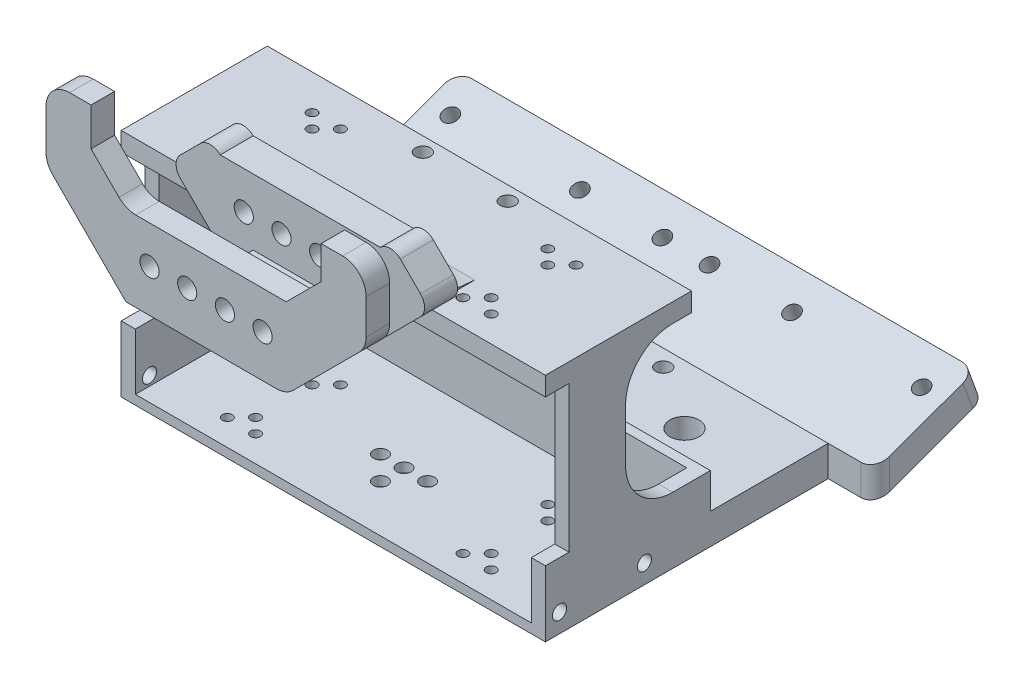
SolidWorks part; units mm, degrees
ref_plane "前视基准面" through (0, 0, 0) normal (0, 0, 1) x (1, 0, 0)
ref_plane "上视基准面" through (0, 0, 0) normal (0, 1, 0) x (1, 0, 0)
ref_plane "右视基准面" through (0, 0, 0) normal (1, 0, 0) x (0, 0, -1)
other "Configuration Table"
sketch "草图1" plane through (0, 0, 0) normal (0, 1, 0) x (1, 0, 0)
  line L1 (-45, 23) -> (45, 23)
  line L2 (-45, 23) -> (-45, -23)
  line L3 (-45, -23) -> (45, -23)
  line L4 (45, 23) -> (45, -23)
  line L5 (-45, 23) -> (45, -23) construction
  line L6 (-45, -23) -> (45, 23) construction
  point P0 (0, 0)
  dimension "D1" = 90
  dimension "D2" = 46
extrude "凸台-拉伸1" add sketch "草图1" along normal blind 4
sketch "草图3" plane through (0, 0, 23) normal (0, 0, 1) x (1, 0, 0)
  line L0 (-45, 0) -> (45, 0) construction
  line L1 (-17, 0) -> (17, 0)
  line L2 (-17, 0) -> (-17, 17) construction
  line L3 (17, 0) -> (17, 17) construction
  line L4 (-17, 17) -> (17, 17)
  line L6 (17, 0) -> (27.6066, 10.6066)
  line L7 (17, 17) -> (19.1066, 19.1066)
  line L9 (27.6066, 10.6066) -> (19.1066, 19.1066)
  line L10 (0, 0) -> (0, 17) construction
  line L11 (-17, 17) -> (-19.1066, 19.1066)
  line L12 (-27.6066, 10.6066) -> (-19.1066, 19.1066)
  line L13 (-17, 0) -> (-27.6066, 10.6066)
  point P0 (-17, 0)
  point P1 (17, 0)
  dimension "D1" = 17
  dimension "D2" = 17
  dimension "D3" = 17
  dimension "D4" = 45
  dimension "D5" = 15
extrude "凸台-拉伸2" add sketch "草图3" along normal blind 7
sketch "草图4" plane through (0, 0, 30) normal (0, 0, 1) x (1, 0, 0)
  line L0 (-18.5, 1.5) -> (18.5, 1.5) construction
  line L1 (-17, 0) -> (17, 0) construction
  line L3 (-27.6066, 10.6066) -> (-17, 0) construction
  line L4 (-10, 3) -> (10, 3)
  line L9 (17, 0) -> (27.6066, 10.6066) construction
  line L10 (-10, 3) -> (-10, 0)
  line L11 (-10, 0) -> (10, 0)
  line L12 (10, 3) -> (10, 0)
  line L13 (-10, 3) -> (10, 0) construction
  line L14 (-10, 0) -> (10, 3) construction
  point P8 (0, 1.5)
  dimension "D1" = 1.5
  dimension "D2" = 20
extrude "凸台-拉伸3" add sketch "草图4" along normal blind 15
sketch "草图5" plane through (0, 0, 45) normal (0, 0, 1) x (1, 0, 0)
  line L4 (-33.9632, 25.4632) -> (-33.9632, 32.4632)
  line L6 (-17, 0) -> (-27.6066, 10.6066)
  line L7 (-27.6066, 10.6066) -> (-17, 0) construction
  line L9 (-19.1066, 19.1066) -> (-17, 17)
  line L10 (-33.9632, 32.4632) -> (-24.4099, 32.4632)
  line L11 (-24.4099, 32.4632) -> (-24.4099, 24.4099)
  line L12 (-17, 17) -> (17, 17)
  line L13 (17, 17) -> (19.1066, 19.1066)
  line L16 (27.6066, 10.6066) -> (17, 0)
  line L17 (17, 0) -> (-17, 0)
  line L19 (-27.6066, 10.6066) -> (-38.2132, 21.2132) construction
  line L20 (-19.1066, 19.1066) -> (-29.7132, 29.7132) construction
  line L21 (-38.2132, 21.2132) -> (-29.7132, 29.7132) construction
  line L23 (19.1066, 19.1066) -> (29.7132, 29.7132) construction
  line L24 (27.6066, 10.6066) -> (38.2132, 21.2132) construction
  line L25 (29.7132, 29.7132) -> (38.2132, 21.2132) construction
  line L27 (24.4099, 24.4099) -> (24.4099, 31.4099)
  line L28 (24.4099, 31.4099) -> (33.9632, 31.4099)
  line L29 (33.9632, 31.4099) -> (33.9632, 25.4632)
  line L30 (-24.4099, 24.4099) -> (-19.1066, 19.1066)
  line L31 (19.1066, 19.1066) -> (24.4099, 24.4099)
  line L33 (-33.9632, 25.4632) -> (-33.9632, 16.9632)
  line L34 (-33.9632, 16.9632) -> (-27.6066, 10.6066)
  line L36 (33.9632, 25.4632) -> (33.9632, 16.9632)
  line L37 (33.9632, 16.9632) -> (27.6066, 10.6066)
  dimension "D1" = 15
  dimension "D2" = 15
  dimension "D3" = 7
  dimension "D4" = 7
extrude "凸台-拉伸4" add sketch "草图5" along normal blind 5
sketch "草图6" plane through (0, 0, 50) normal (0, 0, 1) x (1, 0, 0)
  line L0 (-20, 9) -> (20, 9) construction
  line L2 (-17, 0) -> (17, 0) construction
  circle A0 centre (-12, 9) radius 2.03
  circle A1 centre (-4, 9) radius 2.03
  circle A2 centre (4, 9) radius 2.03
  circle A3 centre (12, 9) radius 2.03
  point P6 (-12, 9)
  point P7 (-4, 9)
  point P8 (4, 9)
  point P9 (12, 9)
  point P10 (0, 9)
  dimension "D5" = 9
  dimension "D1" = 4
  dimension "D2" = 4
  dimension "D3" = 8
  dimension "D4" = 8
extrude "切除-拉伸2" cut sketch "草图6" against normal up to surface (27 mm away) up to face at (0, 12.6783, 23)
sketch "草图8" plane through (0, 0, 23) normal (0, 0, -1) x (-1, 0, 0)
  line L0 (0, 0) -> (0, -12.5)
  line L1 (-45, 0) -> (45, 0) construction
  line L2 (0, -12.5) -> (27, -12.5)
  line L3 (0, -12.5) -> (-27, -12.5)
  dimension "D1" = 12.5
  dimension "D2" = 27
  dimension "D3" = 27
ref_plane "基准面1" through (0, -12.5, 0) normal (0, -1, 0) x (-1, 0, 0)
sketch "草图9" plane through (0, -12.5, 0) normal (0, -1, 0) x (-1, 0, 0)
  line L0 (27, -17) -> (27, -26.6611) construction
  line L1 (-27, -17) -> (-27, -21.8305) construction
sketch "草图11" plane through (0, 0, 0) normal (0, -1, 0) x (1, 0, 0)
  line L0 (-45, 18) -> (-42, 18)
  line L1 (-45, 18) -> (-45, 6)
  line L2 (-42, 18) -> (-42, 6)
  line L3 (-45, 6) -> (-42, 6)
  line L4 (-45, -23) -> (-45, 23) construction
  line L5 (-45, 23) -> (-17, 23) construction
  line L6 (0, 0) -> (0, -23) construction
  line L7 (45, -23) -> (-45, -23) construction
  line L8 (45, 6) -> (42, 6)
  line L9 (42, 18) -> (42, 6)
  line L10 (45, 18) -> (45, 6)
  line L11 (45, 18) -> (42, 18)
  dimension "D1" = 5
  dimension "D2" = 12
  dimension "D3" = 3
extrude "凸台-拉伸5" add sketch "草图11" along normal blind 31
sketch "草图12" plane through (0, -31, 0) normal (0, -1, 0) x (1, 0, 0)
  line L0 (42, -10) -> (42, 23)
  line L9 (-45, 23) -> (-45, -12)
  line L15 (17, 23) -> (45, 23) construction
  line L18 (42, 23) -> (45, 23)
  line L20 (-42, 6) -> (-42, 18) construction
  line L30 (-45, -23) -> (-45, 6) construction
  line L31 (-45, -12) -> (45, -12)
  line L32 (45, 6) -> (45, -23) construction
  line L33 (45, -12) -> (45, 23)
  line L34 (-45, 23) -> (-42, 23)
  line L35 (-45, 23) -> (-17, 23) construction
  line L36 (-42, 23) -> (-42, -10)
  line L37 (-42, -10) -> (42, -10)
  line L38 (42, 18) -> (42, 6) construction
  dimension "D1" = 35
  dimension "D2" = 2
extrude "凸台-拉伸6" add sketch "草图12" along normal blind 12
sketch "草图13" plane through (0, -43, 0) normal (0, -1, 0) x (1, 0, 0)
  line L7 (-45, 23) -> (45, 23)
  line L8 (-45, 23) -> (-45, -12)
  line L9 (-45, -12) -> (45, -12)
  line L10 (45, 23) -> (45, -12)
extrude "凸台-拉伸7" add sketch "草图13" along normal blind 2
sketch "草图14" plane through (0, -45, 0) normal (0, -1, 0) x (1, 0, 0)
  line L0 (0, 8.5) -> (0, -12) construction
  line L2 (0, 8.5) -> (25, 8.5) construction
  line L3 (25, 8.5) -> (25, 14.5) construction
  line L4 (25, 14.5) -> (25, 17.5) construction
  line L5 (25, 17.5) -> (28, 17.5) construction
  line L6 (25, 17.5) -> (22, 17.5) construction
  line L7 (-45, -12) -> (45, -12) construction
  circle A0 centre (22, 17.5) radius 1.05
  circle A1 centre (28, 17.5) radius 1.05
  circle A2 centre (25, 14.5) radius 1.05
  circle A3 centre (22, -0.5) radius 1.05
  circle A4 centre (25, 2.5) radius 1.05
  circle A5 centre (28, -0.5) radius 1.05
  circle A6 centre (-28, -0.5) radius 1.05
  circle A7 centre (-22, -0.5) radius 1.05
  circle A8 centre (-25, 2.5) radius 1.05
  circle A9 centre (-22, 17.5) radius 1.05
  circle A10 centre (-25, 14.5) radius 1.05
  circle A11 centre (-28, 17.5) radius 1.05
  point P0 (0, 8.5)
  dimension "D2" = 6
  dimension "D1" = 25
  dimension "D3" = 3
  dimension "D4" = 3
  dimension "D5" = 3
extrude "切除-拉伸3" cut sketch "草图14" against normal through all both and the other way through all
fillet "圆角3" radius 10 4 edges at (43.5, -31, 6) (-43.5, -31, 6) (43.5, 0, 6) (-43.5, 0, 6)
fillet "圆角5" radius 5 8 edges at (-17, 17, 47.5) (-17, 0, 26.5) (17, 0, 26.5) (17, 0, 47.5) (-33.9632, 32.4632, 47.5) (33.9632, 31.4099, 47.5) (33.9632, 16.9632, 47.5) (-33.9632, 16.9632, 47.5)
fillet "圆角9" radius 3 4 edges at (-27.6066, 10.6066, 26.5) (-19.1066, 19.1066, 26.5) (19.1066, 19.1066, 26.5) (27.6066, 10.6066, 26.5)
sketch "草图16" plane through (0, 4, 0) normal (0, 1, 0) x (1, 0, 0)
  line L0 (45, -23) -> (45, 23) construction
  line L1 (-45, 23) -> (45, 23)
  line L2 (-45, 23) -> (-45, 8)
  line L3 (-45, 8) -> (45, 8)
  line L4 (45, 23) -> (45, 8)
  dimension "D1" = 15
extrude "切除-拉伸4" cut sketch "草图16" against normal up to next
sketch "草图17" plane through (0, 0, -12) normal (0, 0, -1) x (-1, 0, 0)
  line L0 (45, -45) -> (45, -31) construction
  line L1 (-45, -45) -> (45, -45)
  line L2 (-45, -45) -> (-45, -38.5)
  line L3 (-45, -38.5) -> (45, -38.5)
  line L4 (45, -45) -> (45, -38.5)
  dimension "D1" = 6.5
extrude "凸台-拉伸8" add sketch "草图17" along normal blind 25
sketch "草图22" plane through (0, -45, 0) normal (0, -1, 0) x (1, 0, 0)
  line L0 (0, 23) -> (0, 13) construction
  line L1 (45, 23) -> (-45, 23) construction
  circle A0 centre (0, 13) radius 1.5
  circle A1 centre (5, 8) radius 1.5
  circle A2 centre (0, 8) radius 1.5
  circle A3 centre (-5, 8) radius 1.5
  point P5 (0, 8)
  point P6 (5, 8)
  point P7 (-5, 8)
  dimension "D1" = 10
  dimension "D2" = 5
  dimension "D3" = 5
  dimension "D4" = 5
extrude "切除-拉伸6" cut sketch "草图22" against normal up to next
sketch "草图25" plane through (0, 0, 0) normal (0, -1, 0) x (1, 0, 0)
  line L0 (0, 0) -> (0, -10.2866) construction
  line L1 (45, -8) -> (-45, -8) construction
  line L2 (45, -8) -> (45, 23) construction
  line L3 (45, 23) -> (-45, 23) construction
  line L4 (-45, -8) -> (-45, 23) construction
  line L5 (9, -5) -> (-9, -5) construction
  line L6 (9, -5) -> (9, 22) construction
  line L7 (9, 22) -> (-9, 22) construction
  line L8 (-9, -5) -> (-9, 22) construction
  circle A0 centre (-9, 22) radius 1.6
  circle A1 centre (9, 22) radius 1.6
  circle A2 centre (9, -5) radius 1.6
  circle A3 centre (-9, -5) radius 1.6
  point P4 (0, -4)
  point P5 (9, -5)
  point P18 (0, -5)
  dimension "D1" = 3
  dimension "D3" = 27
  dimension "D4" = 18
extrude "切除-拉伸7" cut sketch "草图25" against normal up to surface (4 mm away) up to face at (0, 4, 12.6667)
sketch "草图28" plane through (0, 0, 0) normal (1, 0, 0) x (0, 0, -1)
  line L0 (-23, 4) -> (-13, 4)
  line L1 (-23, 4) -> (8, 4) construction
  line L2 (-13, 4) -> (-23, 5)
  line L3 (-23, 4) -> (-23, 8.4853) construction
  line L4 (-23, 5) -> (-23, 4)
  dimension "D1" = 1
  dimension "D2" = 10
extrude "凸台-拉伸10" add sketch "草图28" along normal mid plane 40
sketch "草图29" plane through (0, 0, 0) normal (1, 0, 0) x (0, 0, -1)
  line L0 (37, -38.5) -> (58.4033, -30.7099)
  line L1 (58.4033, -30.7099) -> (60.4923, -36.4495)
  line L2 (60.4923, -36.4495) -> (37, -45)
  line L3 (37, -38.5) -> (37, -45)
  line L4 (33.2326, -45) -> (47.1106, -45) construction
  dimension "D1" = 25
  dimension "D2" = 70
extrude "凸台-拉伸11" add sketch "草图29" along normal mid plane 110
sketch "草图31" plane through (0, -51.6276, -18.7909) normal (0, -0.9397, -0.342) x (1, 0, 0)
  line L0 (55, -19.3777) -> (45, -19.3777) construction
  line L1 (-55, -44.3777) -> (55, -44.3777) construction
  line L2 (-55, -44.3777) -> (-55, -19.3777) construction
  line L3 (-55, -19.3777) -> (55, -19.3777) construction
  line L4 (55, -44.3777) -> (55, -19.3777) construction
  line L5 (0, -19.3777) -> (0, -44.3777) construction
  line L6 (-55, -37.3777) -> (55, -37.3777) construction
  line L7 (55, -19.3777) -> (55, -44.3777) construction
  circle A0 centre (-50, -37.3777) radius 1.6
  circle A1 centre (-5, -37.3777) radius 1.6
  circle A2 centre (5, -37.3777) radius 1.6
  circle A3 centre (50, -37.3777) radius 1.6
  circle A4 centre (-22.5, -37.3777) radius 1.6
  circle A5 centre (22.5, -37.3777) radius 1.6
  point P11 (5, -37.3777)
  point P12 (50, -37.3777)
  point P13 (-5, -37.3777)
  point P14 (-50, -37.3777)
  point P116 (0, -16.9977)
  dimension "D6" = 22.5
  dimension "D1" = 7
  dimension "D2" = 5
  dimension "D3" = 45
  dimension "D4" = 5
  dimension "D5" = 45
  dimension "D7" = 22.5
extrude "切除-拉伸8" cut sketch "草图31" against normal up to next
sketch "草图32" plane through (0, -38.5, 0) normal (0, 1, 0) x (1, 0, 0)
  line L1 (-45, 37) -> (45, 37) construction
  line L2 (-45, 37) -> (-45, 12) construction
  line L3 (-45, 12) -> (45, 12) construction
  line L4 (45, 37) -> (45, 12) construction
  line L5 (0, 12) -> (0, 37) construction
  line L6 (-45, 24.5) -> (45, 24.5) construction
  line L7 (-13.5, 33.5) -> (13.5, 33.5) construction
  line L8 (-13.5, 33.5) -> (-13.5, 15.5) construction
  line L9 (-13.5, 15.5) -> (13.5, 15.5) construction
  line L10 (13.5, 33.5) -> (13.5, 15.5) construction
  line L11 (-13.5, 33.5) -> (13.5, 15.5) construction
  line L12 (-13.5, 15.5) -> (13.5, 33.5) construction
  circle A0 centre (13.5, 33.5) radius 1.6
  circle A1 centre (13.5, 15.5) radius 1.6
  circle A2 centre (-13.5, 15.5) radius 1.6
  circle A3 centre (-13.5, 33.5) radius 1.6
  circle A4 centre (0, 24.5) radius 3.1
  circle A5 centre (27, 24.5) radius 3.1
  circle A6 centre (-27, 24.5) radius 3.1
  point P4 (0, 24.5)
  point P80 (0, 24.5)
  dimension "D1" = 27
  dimension "D2" = 27
extrude "切除-拉伸9" cut sketch "草图32" against normal up to next
fillet "圆角12" radius 3 4 edges at (55, -41.75, -37) (-55, -41.75, -37) (55, -33.5797, -59.4478) (-55, -33.5797, -59.4478)
sketch "草图33" plane through (45, 0, 0) normal (1, 0, 0) x (0, 0, -1)
  line L0 (37, -45) -> (-23, -45) construction
  line L1 (-23, -45) -> (-23, -31) construction
  circle A0 centre (-2, -41) radius 1.5
  circle A1 centre (-20, -41) radius 1.5
  point P0 (-20, -41)
  dimension "D3" = 18
  dimension "D1" = 4
  dimension "D2" = 3
extrude "切除-拉伸10" cut sketch "草图33" against normal through all
